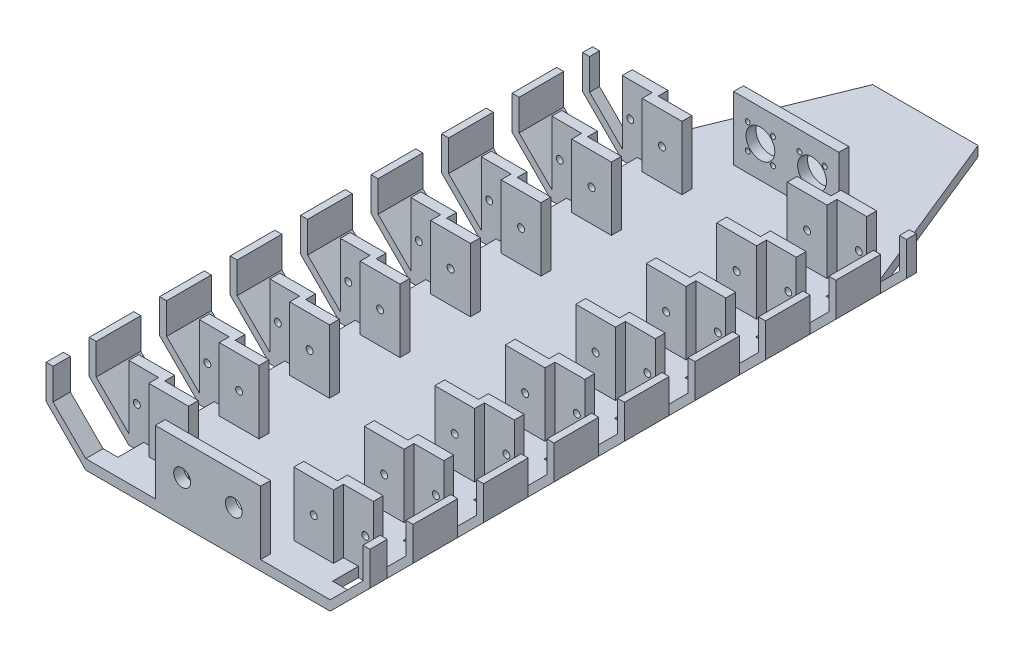
SolidWorks part; units mm, degrees
ref_plane "Front Plane" through (0, 0, 0) normal (0, 0, 1) x (1, 0, 0)
ref_plane "Top Plane" through (0, 0, 0) normal (0, 1, 0) x (1, 0, 0)
ref_plane "Right Plane" through (0, 0, 0) normal (1, 0, 0) x (0, 0, -1)
sketch "Sketch1" plane through (0, 0, 0) normal (0, 1, 0) x (1, 0, 0)
  line L0 (0, -135) -> (0, 135) construction
  line L1 (-13, 135) -> (-36, 135)
  line L2 (13, -135) -> (-13, -135)
  line L3 (13, -135) -> (13, 135) construction
  line L4 (13, 135) -> (-13, 135)
  line L5 (-13, -135) -> (-13, 135) construction
  line L8 (-36, 135) -> (-36, -135) construction
  line L9 (-36, -135) -> (-13, -135)
  line L10 (-36, 135) -> (-61.5, 135)
  line L11 (-61.5, 135) -> (-61.5, -135)
  line L12 (-61.5, -135) -> (-36, -135)
  line L13 (36, -135) -> (13, -135)
  line L14 (61.5, -135) -> (36, -135)
  line L15 (61.5, 135) -> (61.5, -135)
  line L16 (36, 135) -> (36, -135) construction
  line L17 (13, 135) -> (36, 135)
  line L18 (36, 135) -> (61.5, 135)
  point P0 (0, 0)
  point P3 (0, -138)
  point P4 (0, 0)
  point P18 (0, -138)
  dimension "D1" = 270
  dimension "D2" = 26
  dimension "D3" = 23
  dimension "D4" = 123
extrude "Boss-Extrude1" add sketch "Sketch1" along normal blind 5
sketch "Sketch2" plane through (0, 5, 0) normal (0, 1, 0) x (1, 0, 0)
  line L0 (61.5, -135) -> (61.5, 135) construction
  line L1 (-61.5, -135) -> (61.5, -135)
  line L2 (-61.5, -135) -> (-61.5, -130)
  line L3 (-61.5, -130) -> (61.5, -130)
  line L4 (61.5, -135) -> (61.5, -130)
  line L5 (-61.5, 135) -> (-36.5, 135) construction
  line L6 (-61.5, 135) -> (61.5, 135) construction
  line L7 (-61.5, 135) -> (-61.5, 130) construction
  line L8 (-61.5, 130) -> (61.5, 130) construction
  line L9 (61.5, 135) -> (61.5, 130) construction
  line L10 (-36.5, 135) -> (-26.5, 135)
  line L11 (-36.5, 135) -> (-46.5, 135)
  line L12 (-46.5, 135) -> (-46.5, 130)
  line L13 (-46.5, 130) -> (-26.5, 130)
  line L14 (-26.5, 130) -> (-26.5, 135)
  line L15 (0, 135) -> (0, 130) construction
  line L16 (46.5, 130) -> (26.5, 130)
  line L17 (46.5, 135) -> (46.5, 130)
  line L18 (36.5, 135) -> (46.5, 135)
  line L19 (36.5, 135) -> (26.5, 135)
  line L20 (26.5, 130) -> (26.5, 135)
  line L21 (-26.5, 130) -> (-26.5, -130) construction
  dimension "D1" = 5
  dimension "D2" = 5
  dimension "D3" = 25
  dimension "D4" = 10
  dimension "D5" = 10
extrude "Boss-Extrude2" add sketch "Sketch2" along normal blind 32
sketch "Sketch3" plane through (0, 0, 135) normal (0, 0, 1) x (1, 0, 0)
  line L0 (0, 37) -> (0, 0) construction
  line L2 (-61.5, 37) -> (-61.5, 5) construction
  line L3 (-61.5, 37) -> (61.5, 37) construction
  line L5 (-61.5, 37) -> (-61.5, 0) construction
  line L6 (-61.5, 21) -> (61.5, 21) construction
  line L7 (61.5, 37) -> (61.5, 0) construction
  circle A0 centre (-13, 21) radius 4.25
  circle A1 centre (13, 21) radius 4.25
  dimension "D1" = 8.5
  dimension "D2" = 8.5
  dimension "D3" = 26
  dimension "D4" = 13
  dimension "D5" = 32
  dimension "D6" = 16
sketch "Sketch8" plane through (0, 0, -130) normal (0, 0, 1) x (1, 0, 0)
  line L0 (0, 37) -> (0, 5) construction
  line L2 (0, 21) -> (-61.5, 21) construction
  line L3 (-61.5, 37) -> (-61.5, 0) construction
  line L4 (-36.5, 37) -> (-36.5, 5) construction
  line L5 (-46.5, 37) -> (-26.5, 37) construction
  line L6 (-46.5, 5) -> (-26.5, 5) construction
  line L7 (-61.5, 37) -> (61.5, 37) construction
  circle A0 centre (-36.5, 21) radius 1.75
  circle A1 centre (36.5, 21) radius 1.75
  dimension "D2" = 3.5
  dimension "D1" = 32
sketch "Sketch9" plane through (0, 0, -135) normal (0, 0, -1) x (-1, 0, 0)
  line L1 (-61.5, 5) -> (61.5, 5)
  line L2 (-61.5, 5) -> (-61.5, 0)
  line L3 (-61.5, 0) -> (61.5, 0)
  line L4 (61.5, 5) -> (61.5, 0)
extrude "Boss-Extrude4" add sketch "Sketch9" along normal blind 5
sketch "Sketch10" plane through (0, 5, 0) normal (0, 1, 0) x (1, 0, 0)
  line L0 (-26.5, 135) -> (-46.5, 135) construction
  line L1 (-61.5, 140) -> (-43.5, 140)
  line L2 (-61.5, 140) -> (-61.5, 135)
  line L3 (-61.5, 135) -> (-43.5, 135)
  line L4 (-43.5, 140) -> (-43.5, 135)
  line L5 (26.5, 135) -> (46.5, 135) construction
  line L6 (61.5, 140) -> (43.5, 140)
  line L7 (61.5, 140) -> (61.5, 135)
  line L8 (61.5, 135) -> (43.5, 135)
  line L9 (43.5, 140) -> (43.5, 135)
  line L10 (-46.5, 135) -> (-46.5, 130) construction
  line L11 (46.5, 130) -> (46.5, 135) construction
  dimension "D1" = 3
  dimension "D2" = 3
extrude "Boss-Extrude8" add sketch "Sketch10" along normal blind 32
sketch "Sketch11" plane through (0, 5, 0) normal (0, 1, 0) x (1, 0, 0)
  line L0 (0, 140) -> (0, -130) construction
  line L1 (-43.5, 140) -> (43.5, 140) construction
  line L2 (61.5, -130) -> (-61.5, -130) construction
  line L3 (-61.5, 140) -> (-61.5, 135) construction
  line L4 (-61.5, 135) -> (-46.5, 135) construction
  line L5 (-46.5, 135) -> (-46.5, 130) construction
  line L6 (-46.5, 130) -> (-26.5, 130) construction
  line L7 (-26.5, 130) -> (-26.5, 135) construction
  line L8 (-26.5, 135) -> (-43.5, 135) construction
  line L9 (-43.5, 135) -> (-43.5, 140) construction
  line L10 (-43.5, 140) -> (-61.5, 140) construction
  line L11 (-26.5, -130) -> (-26.5, -109.8199)
  line L12 (-43.5, 104.5294) -> (-61.5, 104.5294)
  line L13 (-61.5, 104.5294) -> (-61.5, 99.5294)
  line L14 (-61.5, 99.5294) -> (-46.5, 99.5294)
  line L15 (-46.5, 99.5294) -> (-46.5, 94.5294)
  line L16 (-46.5, 94.5294) -> (-26.5, 94.5294)
  line L17 (-26.5, 94.5294) -> (-26.5, 99.5294)
  line L18 (-26.5, 99.5294) -> (-43.5, 99.5294)
  line L19 (-43.5, 99.5294) -> (-43.5, 104.5294)
  line L20 (-43.5, 69.0588) -> (-61.5, 69.0588)
  line L21 (-61.5, 69.0588) -> (-61.5, 64.0588)
  line L22 (-61.5, 64.0588) -> (-46.5, 64.0588)
  line L23 (-46.5, 64.0588) -> (-46.5, 59.0588)
  line L24 (-46.5, 59.0588) -> (-26.5, 59.0588)
  line L25 (-26.5, 59.0588) -> (-26.5, 64.0588)
  line L26 (-26.5, 64.0588) -> (-43.5, 64.0588)
  line L27 (-43.5, 64.0588) -> (-43.5, 69.0588)
  line L28 (-43.5, 33.5882) -> (-61.5, 33.5882)
  line L29 (-61.5, 33.5882) -> (-61.5, 28.5882)
  line L30 (-61.5, 28.5882) -> (-46.5, 28.5882)
  line L31 (-46.5, 28.5882) -> (-46.5, 23.5882)
  line L32 (-46.5, 23.5882) -> (-26.5, 23.5882)
  line L33 (-26.5, 23.5882) -> (-26.5, 28.5882)
  line L34 (-26.5, 28.5882) -> (-43.5, 28.5882)
  line L35 (-43.5, 28.5882) -> (-43.5, 33.5882)
  line L36 (-43.5, -1.8824) -> (-61.5, -1.8824)
  line L37 (-61.5, -1.8824) -> (-61.5, -6.8824)
  line L38 (-61.5, -6.8824) -> (-46.5, -6.8824)
  line L39 (-46.5, -6.8824) -> (-46.5, -11.8824)
  line L40 (-46.5, -11.8824) -> (-26.5, -11.8824)
  line L41 (-26.5, -11.8824) -> (-26.5, -6.8824)
  line L42 (-26.5, -6.8824) -> (-43.5, -6.8824)
  line L43 (-43.5, -6.8824) -> (-43.5, -1.8824)
  line L44 (-43.5, -37.3529) -> (-61.5, -37.3529)
  line L45 (-61.5, -37.3529) -> (-61.5, -42.3529)
  line L46 (-61.5, -42.3529) -> (-46.5, -42.3529)
  line L47 (-46.5, -42.3529) -> (-46.5, -47.3529)
  line L48 (-46.5, -47.3529) -> (-26.5, -47.3529)
  line L49 (-26.5, -47.3529) -> (-26.5, -42.3529)
  line L50 (-26.5, -42.3529) -> (-43.5, -42.3529)
  line L51 (-43.5, -42.3529) -> (-43.5, -37.3529)
  line L52 (-43.5, -72.8235) -> (-61.5, -72.8235)
  line L53 (-61.5, -72.8235) -> (-61.5, -77.8235)
  line L54 (-61.5, -77.8235) -> (-46.5, -77.8235)
  line L55 (-46.5, -77.8235) -> (-46.5, -82.8235)
  line L56 (-46.5, -82.8235) -> (-26.5, -82.8235)
  line L57 (-26.5, -82.8235) -> (-26.5, -77.8235)
  line L58 (-26.5, -77.8235) -> (-43.5, -77.8235)
  line L59 (-43.5, -77.8235) -> (-43.5, -72.8235)
  line L60 (-43.5, -108.2941) -> (-61.5, -108.2941)
  line L61 (-61.5, -108.2941) -> (-61.5, -113.2941)
  line L62 (-61.5, -113.2941) -> (-46.5, -113.2941)
  line L63 (-46.5, -113.2941) -> (-46.5, -118.2941)
  line L64 (-46.5, -118.2941) -> (-26.5, -118.2941)
  line L65 (-26.5, -118.2941) -> (-26.5, -113.2941)
  line L66 (-26.5, -113.2941) -> (-43.5, -113.2941)
  line L67 (-43.5, -113.2941) -> (-43.5, -108.2941)
  line L68 (43.5, -113.2941) -> (43.5, -108.2941)
  line L69 (26.5, -113.2941) -> (43.5, -113.2941)
  line L70 (26.5, -118.2941) -> (26.5, -113.2941)
  line L71 (46.5, -118.2941) -> (26.5, -118.2941)
  line L72 (46.5, -113.2941) -> (46.5, -118.2941)
  line L73 (61.5, -113.2941) -> (46.5, -113.2941)
  line L74 (61.5, -108.2941) -> (61.5, -113.2941)
  line L75 (43.5, -108.2941) -> (61.5, -108.2941)
  line L76 (43.5, -77.8235) -> (43.5, -72.8235)
  line L77 (26.5, -77.8235) -> (43.5, -77.8235)
  line L78 (26.5, -82.8235) -> (26.5, -77.8235)
  line L79 (46.5, -82.8235) -> (26.5, -82.8235)
  line L80 (46.5, -77.8235) -> (46.5, -82.8235)
  line L81 (61.5, -77.8235) -> (46.5, -77.8235)
  line L82 (61.5, -72.8235) -> (61.5, -77.8235)
  line L83 (43.5, -72.8235) -> (61.5, -72.8235)
  line L84 (43.5, -42.3529) -> (43.5, -37.3529)
  line L85 (26.5, -42.3529) -> (43.5, -42.3529)
  line L86 (26.5, -47.3529) -> (26.5, -42.3529)
  line L87 (46.5, -47.3529) -> (26.5, -47.3529)
  line L88 (46.5, -42.3529) -> (46.5, -47.3529)
  line L89 (61.5, -42.3529) -> (46.5, -42.3529)
  line L90 (61.5, -37.3529) -> (61.5, -42.3529)
  line L91 (43.5, -37.3529) -> (61.5, -37.3529)
  line L92 (43.5, -6.8824) -> (43.5, -1.8824)
  line L93 (26.5, -6.8824) -> (43.5, -6.8824)
  line L94 (26.5, -11.8824) -> (26.5, -6.8824)
  line L95 (46.5, -11.8824) -> (26.5, -11.8824)
  line L96 (46.5, -6.8824) -> (46.5, -11.8824)
  line L97 (61.5, -6.8824) -> (46.5, -6.8824)
  line L98 (61.5, -1.8824) -> (61.5, -6.8824)
  line L99 (43.5, -1.8824) -> (61.5, -1.8824)
  line L100 (43.5, 28.5882) -> (43.5, 33.5882)
  line L101 (26.5, 28.5882) -> (43.5, 28.5882)
  line L102 (26.5, 23.5882) -> (26.5, 28.5882)
  line L103 (46.5, 23.5882) -> (26.5, 23.5882)
  line L104 (46.5, 28.5882) -> (46.5, 23.5882)
  line L105 (61.5, 28.5882) -> (46.5, 28.5882)
  line L106 (61.5, 33.5882) -> (61.5, 28.5882)
  line L107 (43.5, 33.5882) -> (61.5, 33.5882)
  line L108 (43.5, 64.0588) -> (43.5, 69.0588)
  line L109 (26.5, 64.0588) -> (43.5, 64.0588)
  line L110 (26.5, 59.0588) -> (26.5, 64.0588)
  line L111 (46.5, 59.0588) -> (26.5, 59.0588)
  line L112 (46.5, 64.0588) -> (46.5, 59.0588)
  line L113 (61.5, 64.0588) -> (46.5, 64.0588)
  line L114 (61.5, 69.0588) -> (61.5, 64.0588)
  line L115 (43.5, 69.0588) -> (61.5, 69.0588)
  line L116 (43.5, 99.5294) -> (43.5, 104.5294)
  line L117 (26.5, 99.5294) -> (43.5, 99.5294)
  line L118 (26.5, 94.5294) -> (26.5, 99.5294)
  line L119 (46.5, 94.5294) -> (26.5, 94.5294)
  line L120 (46.5, 99.5294) -> (46.5, 94.5294)
  line L121 (61.5, 99.5294) -> (46.5, 99.5294)
  line L122 (61.5, 104.5294) -> (61.5, 99.5294)
  line L123 (43.5, 104.5294) -> (61.5, 104.5294)
  point P136 (-54, 135)
  line M11 (-61.5, 135) -> (-61.5, -130)
  line M13 (61.5, -130) -> (61.5, 135)
  dimension "D1" = 20.1801
  dimension "D3" = 30.4706
  dimension "D2" = 8
extrude "Boss-Extrude9" add sketch "Sketch11" along normal blind 32 contours L18 L19 L12 L14 L15 L16 L17 M11 | L26 L27 L20 L22 L23 L24 L25 M11 | L34 L35 L28 L30 L31 L32 L33 M11 | L42 L43 L36 L38 L39 L40 L41 M11 | L50 L51 L44 L46 L47 L48 L49 M11 | L58 L59 L52 L54 L55 L56 L57 M11 | L66 L67 L60 L62 L63 L64 L11 M11 | L75 L68 L69 L70 L71 L72 L73 M13 | L83 L76 L77 L78 L79 L80 L81 M13 | L91 L84 L85 L86 L87 L88 L89 M13 | L107 L100 L101 L102 L103 L104 L105 M13 | L115 L108 L109 L110 L111 L112 L113 M13 | L123 L116 L117 L118 L119 L120 L121 M13 | L93 L92 L99 L98 L97 L96 L95 L94 region at (-44.0789, 5, 113.4257) region at (-44.0789, 5, -99.3978) region at (-44.0789, 5, -63.9272) region at (-44.0789, 5, -28.4567) region at (-44.0789, 5, 7.0139) region at (-44.0789, 5, 42.4845) region at (-44.0789, 5, 77.9551) region at (44.0789, 5, -99.3978) region at (44.0789, 5, -63.9272) region at (44.0789, 5, -28.4567) region at (44.0789, 5, 42.4845) region at (44.0789, 5, 77.9551) region at (44.0789, 5, 113.4257)
extrude "Cut-Extrude4" cut sketch "Sketch8" against normal blind 32 and the other way blind 250
sketch "Sketch13" plane through (0, 0, 135) normal (0, 0, 1) x (1, 0, 0)
  line L0 (-61.5, 37) -> (-61.5, 5)
  line L1 (-61.5, 37) -> (-61.5, 0) construction
  line L2 (-61.5, 37) -> (-26.5, 37)
  line L3 (-61.5, 37) -> (61.5, 37) construction
  line L4 (-26.5, 37) -> (-26.5, 5)
  line L5 (-26.5, 5) -> (-61.5, 5)
  line L6 (0, 37) -> (0, 5.5161) construction
  line L7 (26.5, 37) -> (26.5, 5)
  line L8 (61.5, 37) -> (26.5, 37)
  line L9 (61.5, 37) -> (61.5, 5)
  line L10 (26.5, 5) -> (61.5, 5)
  dimension "D1" = 32
  dimension "D2" = 35
extrude "Cut-Extrude5" cut sketch "Sketch13" against normal blind 11
sketch "Sketch14" plane through (0, 0, 135) normal (0, 0, 1) x (1, 0, 0)
  line L0 (0, 37) -> (0, 0) construction
  line L1 (-26.5, 37) -> (26.5, 37) construction
  line L2 (-81.5, 37) -> (0, 37) construction
  line L3 (-61.5, 0) -> (-81.5, 20)
  line L5 (-77.96, 21.46) -> (-61.5, 5)
  line L6 (-61.5, 37) -> (-61.5, 5) construction
  line L7 (-61.5, 5) -> (-61.5, 0)
  line L12 (-81.5, 20) -> (-81.5, 37)
  line L13 (-81.5, 37) -> (-77.96, 37)
  line L14 (-77.96, 37) -> (-77.96, 21.46)
  line L15 (77.96, 37) -> (77.96, 21.46)
  line L16 (81.5, 37) -> (77.96, 37)
  line L17 (81.5, 20) -> (81.5, 37)
  line L18 (61.5, 0) -> (81.5, 20)
  line L19 (61.5, 5) -> (61.5, 0)
  line L20 (77.96, 21.46) -> (61.5, 5)
  dimension "D1" = 28.2843
  dimension "D2" = 45
  dimension "D3" = 3.54
  dimension "D4" = 20
  dimension "D5" = 3.5355
extrude "Boss-Extrude10" add sketch "Sketch14" against normal blind 275
sketch "Sketch15" plane through (0, 5, 0) normal (0, 1, 0) x (1, 0, 0)
  line L0 (-54, 135) -> (-54, 122)
  line L1 (-61.5, 135) -> (-46.5, 135) construction
  line L2 (-54, 122) -> (-81.5, 122)
  line L4 (-81.5, 122) -> (-81.5, 135)
  line L5 (-81.5, 135) -> (-54, 135)
  line L6 (-81.5, 99.5294) -> (-54, 99.5294)
  line L7 (-54, 99.5294) -> (-54, 86.5294)
  line L8 (-54, 86.5294) -> (-81.5, 86.5294)
  line L9 (-81.5, 86.5294) -> (-81.5, 99.5294)
  line L10 (-81.5, 64.0588) -> (-54, 64.0588)
  line L11 (-54, 64.0588) -> (-54, 51.0588)
  line L12 (-54, 51.0588) -> (-81.5, 51.0588)
  line L13 (-81.5, 51.0588) -> (-81.5, 64.0588)
  line L14 (-81.5, 28.5882) -> (-54, 28.5882)
  line L15 (-54, 28.5882) -> (-54, 15.5882)
  line L16 (-54, 15.5882) -> (-81.5, 15.5882)
  line L17 (-81.5, 15.5882) -> (-81.5, 28.5882)
  line L18 (-81.5, -6.8824) -> (-54, -6.8824)
  line L19 (-54, -6.8824) -> (-54, -19.8824)
  line L20 (-54, -19.8824) -> (-81.5, -19.8824)
  line L21 (-81.5, -19.8824) -> (-81.5, -6.8824)
  line L22 (-81.5, -42.3529) -> (-54, -42.3529)
  line L23 (-54, -42.3529) -> (-54, -55.3529)
  line L24 (-54, -55.3529) -> (-81.5, -55.3529)
  line L25 (-81.5, -55.3529) -> (-81.5, -42.3529)
  line L26 (-81.5, -77.8235) -> (-54, -77.8235)
  line L27 (-54, -77.8235) -> (-54, -90.8235)
  line L28 (-54, -90.8235) -> (-81.5, -90.8235)
  line L29 (-81.5, -90.8235) -> (-81.5, -77.8235)
  line L30 (-81.5, -113.2941) -> (-54, -113.2941)
  line L31 (-54, -113.2941) -> (-54, -126.2941)
  line L32 (-54, -126.2941) -> (-81.5, -126.2941)
  line L33 (-81.5, -126.2941) -> (-81.5, -113.2941)
  line L34 (0, 140) -> (0, -135) construction
  line L35 (-43.5, 140) -> (43.5, 140) construction
  line L36 (-26.5, -135) -> (26.5, -135) construction
  line L37 (81.5, -126.2941) -> (81.5, -113.2941)
  line L38 (54, -126.2941) -> (81.5, -126.2941)
  line L39 (54, -113.2941) -> (54, -126.2941)
  line L40 (81.5, -113.2941) -> (54, -113.2941)
  line L41 (81.5, -90.8235) -> (81.5, -77.8235)
  line L42 (54, -90.8235) -> (81.5, -90.8235)
  line L43 (54, -77.8235) -> (54, -90.8235)
  line L44 (81.5, -77.8235) -> (54, -77.8235)
  line L45 (81.5, -55.3529) -> (81.5, -42.3529)
  line L46 (54, -55.3529) -> (81.5, -55.3529)
  line L47 (54, -42.3529) -> (54, -55.3529)
  line L48 (81.5, -42.3529) -> (54, -42.3529)
  line L49 (81.5, -19.8824) -> (81.5, -6.8824)
  line L50 (54, -19.8824) -> (81.5, -19.8824)
  line L51 (54, -6.8824) -> (54, -19.8824)
  line L52 (81.5, -6.8824) -> (54, -6.8824)
  line L53 (81.5, 15.5882) -> (81.5, 28.5882)
  line L54 (54, 15.5882) -> (81.5, 15.5882)
  line L55 (54, 28.5882) -> (54, 15.5882)
  line L56 (81.5, 28.5882) -> (54, 28.5882)
  line L57 (81.5, 51.0588) -> (81.5, 64.0588)
  line L58 (54, 51.0588) -> (81.5, 51.0588)
  line L59 (54, 64.0588) -> (54, 51.0588)
  line L60 (81.5, 64.0588) -> (54, 64.0588)
  line L61 (81.5, 86.5294) -> (81.5, 99.5294)
  line L62 (54, 86.5294) -> (81.5, 86.5294)
  line L63 (54, 99.5294) -> (54, 86.5294)
  line L64 (81.5, 99.5294) -> (54, 99.5294)
  line L65 (81.5, 122) -> (81.5, 135)
  line L66 (54, 122) -> (81.5, 122)
  line L67 (54, 135) -> (54, 122)
  line L68 (81.5, 135) -> (54, 135)
  line L69 (-61.5, -113.2941) -> (-46.5, -113.2941) construction
  line L70 (-81.5, 140) -> (-81.5, -135) construction
  dimension "D1" = 13
  dimension "D2" = 8
extrude "Cut-Extrude6" cut sketch "Sketch15" against normal through all both and the other way through all
sketch "Sketch16" plane through (0, 0, 113.2941) normal (0, 0, 1) x (1, 0, 0)
  line L0 (-61.5, 21) -> (0, 21) construction
  line L1 (-61.5, 37) -> (-61.5, 5) construction
  line L2 (0, 37) -> (0, 0) construction
  line L3 (-26.5, 37) -> (26.5, 37) construction
  circle A0 centre (-57.5, 20) radius 1.75
  circle A1 centre (57.5, 20) radius 1.75
  point P9 (-36.5, 21)
  dimension "D3" = 3.5
  dimension "D1" = 1
  dimension "D2" = 21
extrude "Cut-Extrude7" cut sketch "Sketch16" against normal through all both and the other way through all
sketch "Sketch17" plane through (0, 5, 0) normal (0, 1, 0) x (1, 0, 0)
  line L0 (-26.5, 130) -> (26.5, 130) construction
  line L1 (0, 130) -> (0, 161) construction
  line L2 (-26.5, -135) -> (-26.5, 161) construction
  line L3 (26.5, -135) -> (26.5, 161) construction
  line L4 (26.5, 161) -> (-26.5, 161) construction
  line L5 (0, 161) -> (0, 226) construction
  line L6 (-61.5, 140) -> (-26.5, 226)
  line L7 (-26.5, 226) -> (0, 226)
  line L8 (0, 226) -> (26.5, 226)
  line L9 (26.5, 226) -> (61.5, 140)
  line L10 (26.5, 161) -> (26.5, 226) construction
  line L11 (-26.5, 161) -> (-26.5, 226) construction
  line L12 (-61.5, 140) -> (61.5, 140)
  dimension "D1" = 31
  dimension "D2" = 296
  dimension "D3" = 90
  dimension "D4" = 65
extrude "Boss-Extrude13" add sketch "Sketch17" against normal blind 5 contours L12 L9 L8 L7 L6
sketch "Sketch18" plane through (0, 5, 0) normal (0, 1, 0) x (1, 0, 0)
  line L0 (-26.5, 130) -> (26.5, 130) construction
  line L1 (0, 130) -> (0, 161) construction
  line L2 (-26.5, 135) -> (-26.5, 161) construction
  line L3 (26.5, 135) -> (26.5, 161) construction
  line L4 (-26.5, 161) -> (-26.5, 156)
  line L5 (-26.5, 156) -> (26.5, 156)
  line L6 (26.5, 156) -> (26.5, 161)
  line L7 (26.5, 161) -> (-26.5, 161)
  dimension "D1" = 31
  dimension "D2" = 5
extrude "Boss-Extrude14" add sketch "Sketch18" along normal blind 32
extrude "Cut-Extrude8" cut sketch "Sketch3" against normal blind 334
sketch "Sketch19" plane through (0, 0, -156) normal (0, 0, 1) x (1, 0, 0)
  line L0 (0, 37) -> (0, 0) construction
  line L1 (-26.5, 37) -> (26.5, 37) construction
  line L3 (-6.636, 14.636) -> (-19.364, 14.636) construction
  line L4 (-6.636, 14.636) -> (-6.636, 27.364) construction
  line L5 (-6.636, 27.364) -> (-19.364, 27.364) construction
  line L6 (-19.364, 14.636) -> (-19.364, 27.364) construction
  line L7 (-6.636, 14.636) -> (-19.364, 27.364) construction
  line L8 (-6.636, 27.364) -> (-19.364, 14.636) construction
  circle A0 centre (-13, 21) radius 7.25
  circle A1 centre (-6.636, 14.636) radius 1.25
  circle A2 centre (-6.636, 27.364) radius 1.25
  circle A3 centre (-19.364, 27.364) radius 1.25
  circle A4 centre (-19.364, 14.636) radius 1.25
  circle A5 centre (13, 21) radius 7.25
  circle A6 centre (19.364, 14.636) radius 1.25
  circle A7 centre (6.636, 14.636) radius 1.25
  circle A8 centre (6.636, 27.364) radius 1.25
  circle A9 centre (19.364, 27.364) radius 1.25
  dimension "D1" = 14.5
  dimension "D4" = 2.5
  dimension "D5" = 2.5
  dimension "D6" = 2.5
  dimension "D7" = 2.5
  dimension "D2" = 18
  dimension "D3" = 18
  dimension "D8" = 12.7279
extrude "Cut-Extrude9" cut sketch "Sketch19" against normal blind 334
